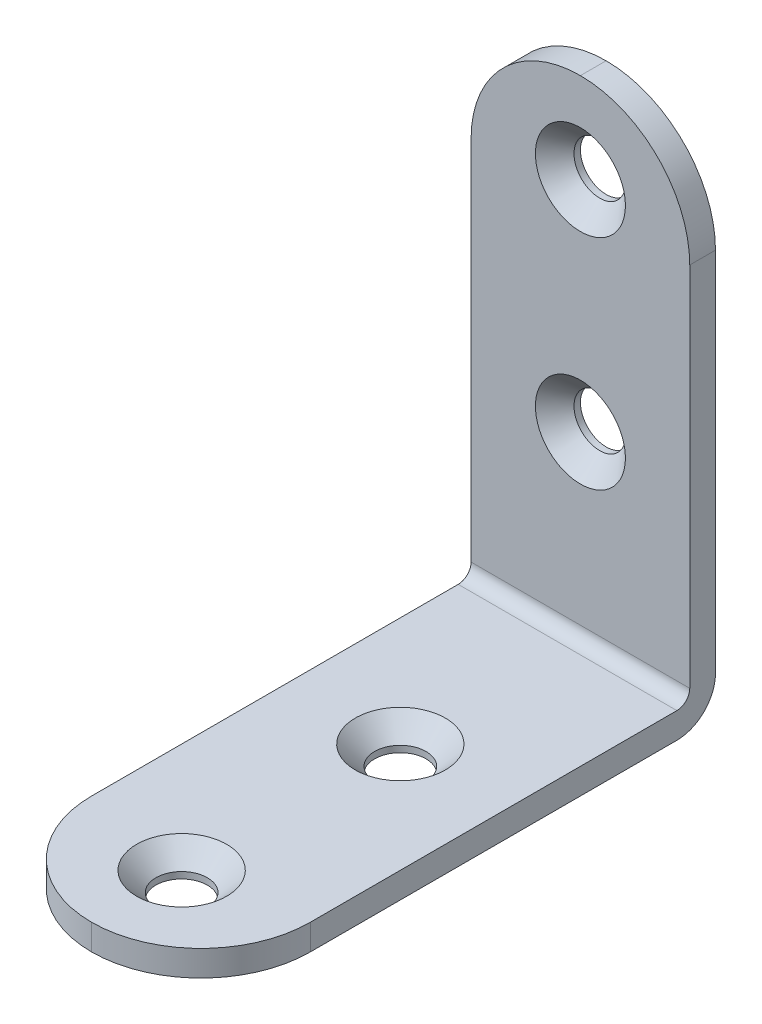
SolidWorks part; units mm, degrees
ref_plane "前视基准面" through (0, 0, 0) normal (0, 0, 1) x (1, 0, 0)
ref_plane "上视基准面" through (0, 0, 0) normal (0, 1, 0) x (1, 0, 0)
ref_plane "右视基准面" through (0, 0, 0) normal (1, 0, 0) x (0, 0, -1)
sketch "草图1" plane through (0, 0, 0) normal (1, 0, 0) x (0, 0, -1)
  line L0 (-40, 0) -> (-3, 0)
  line L1 (0, 3) -> (0, 40)
  line L2 (-40, 2) -> (-3, 2)
  line L3 (-2, 3) -> (-2, 40)
  line L4 (-40, 0) -> (-40, 2)
  line L5 (0, 40) -> (-2, 40)
  arc A0 (-3, 0) -> (0, 3) centre (-3, 3) ccw
  arc A1 (-3, 2) -> (-2, 3) centre (-3, 3) ccw
  point P10 (0, 0)
  dimension "D1" = 40
  dimension "D2" = 40
  dimension "D3" = 2
extrude "凸台-拉伸1" add sketch "草图1" along normal blind 8.5 and the other way blind 8.5
sketch "草图3" plane through (0, 2, 0) normal (0, 1, 0) x (1, 0, 0)
  line L0 (0, 5.2738) -> (0, -38.9564) construction
  line L3 (-8.5, -40) -> (8.5, -40) construction
  circle A0 centre (0, -33) radius 2
  circle A1 centre (0, -16) radius 2
  dimension "D1" = 4
  dimension "D2" = 7
  dimension "D4" = 17
  dimension "D3" = 2
extrude "切除-拉伸2" cut sketch "草图3" against normal blind 15.5
sketch "草图4" plane through (0, 0, 2) normal (0, 0, 1) x (1, 0, 0)
  line L0 (0, -4.5637) -> (0, 33) construction
  line L2 (-8.5, 40) -> (8.5, 40) construction
  circle A0 centre (0, 33) radius 2
  circle A1 centre (0, 16) radius 2
  dimension "D1" = 4
  dimension "D2" = 7
  dimension "D4" = 17
  dimension "D3" = 2
extrude "切除-拉伸3" cut sketch "草图4" against normal blind 15.5
fillet "圆角1" radius 8.5 4 edges at (8.5, 40, 1) (-8.5, 40, 1) (8.5, 1, 40) (-8.5, 1, 40)
chamfer "倒角1" distance 1.5 angle 45 4 edges at (2, 33, 2) (0, 2, 35) (0, 2, 18) (2, 16, 2)
